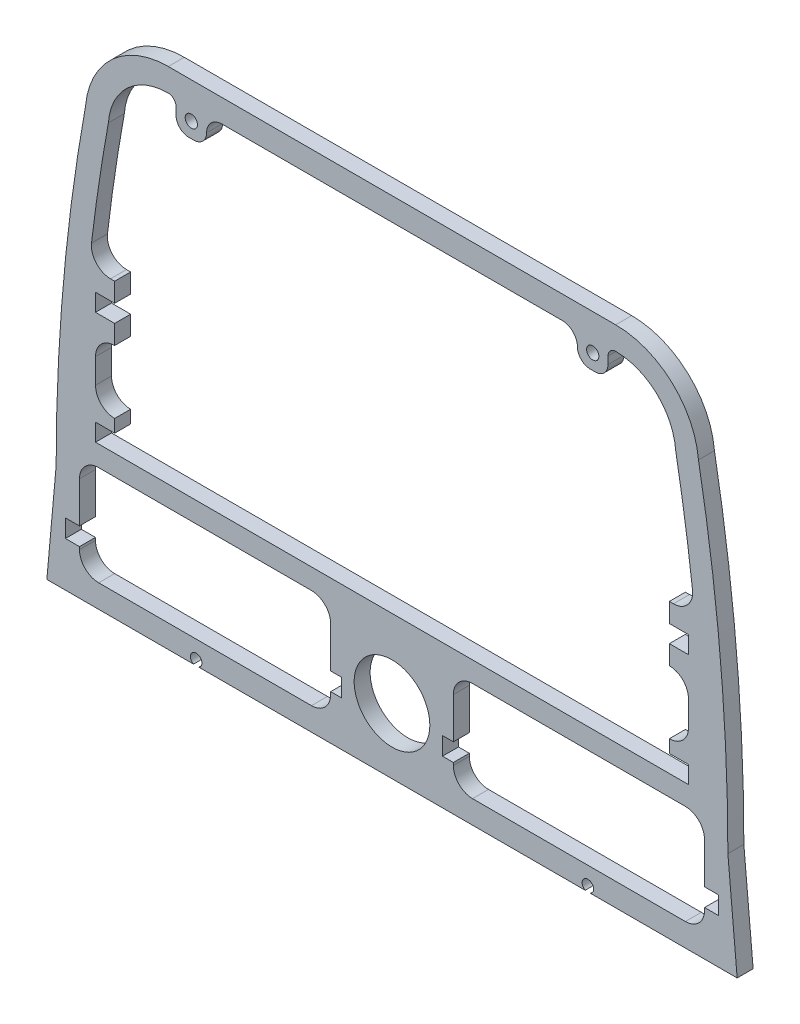
SolidWorks part; units mm, degrees
material "Delrin 2700 NC010, Low Viscosity Acetal Copolymer (SS)"
ref_plane "Front Plane" through (0, 0, 0) normal (0, 0, 1) x (1, 0, 0)
ref_plane "Top Plane" through (0, 0, 0) normal (0, 1, 0) x (1, 0, 0)
ref_plane "Right Plane" through (0, 0, 0) normal (1, 0, 0) x (0, 0, -1)
sketch "Sketch1" plane through (0, 0, 0) normal (0, 0, 1) x (1, 0, 0)
  line L0 (33.3676, -11.9888) -> (34.29, -22.225)
  line L1 (22.225, 27.94) -> (-22.225, 27.94)
  line L2 (-34.29, -22.225) -> (-30.4467, 20.4259) construction
  line L3 (-33.3676, -11.9888) -> (-33.3676, 14.6458) construction
  line L4 (-33.3676, -11.9888) -> (-34.29, -22.225)
  line L5 (16.9079, 25.654) -> (-16.9079, 25.654)
  line L6 (6.096, -17.78) -> (6.096, -19.939)
  line L7 (-31.0499, -19.939) -> (-6.096, -19.939)
  line L8 (-34.29, -22.225) -> (34.29, -22.225)
  line L9 (-31.0499, -10.033) -> (-31.0499, -16.002)
  line L10 (18.4213, 24.1407) -> (18.4213, 24.1363)
  line L11 (19.6913, 22.8663) -> (20.1867, 22.8663)
  line L12 (21.4567, 24.1363) -> (21.4567, 24.8713)
  line L13 (-21.4567, 24.1363) -> (-21.4567, 24.8713)
  line L14 (-19.6913, 22.8663) -> (-20.1867, 22.8663)
  line L15 (-18.4213, 24.1407) -> (-18.4213, 24.1363)
  line L16 (29.4572, -8.001) -> (-29.4572, -8.001)
  line L17 (31.0499, -10.033) -> (6.096, -10.033)
  line L18 (0, 18.415) -> (0, -18.415) construction
  line L19 (-1007.9925, 0) -> (48992.0075, 0) construction
  line L20 (-6.096, -10.033) -> (-31.0499, -10.033)
  line L21 (19.939, 24.384) -> (21.4567, 24.384) construction
  line L22 (6.096, -19.939) -> (31.0499, -19.939)
  line L23 (-6.096, -10.033) -> (-6.096, -16.002)
  line L24 (5.9491, -2.2098) -> (59.5431, -2.2098) construction
  line L25 (5.9491, -2.2098) -> (5.9491, -11.9888) construction
  line L26 (3.4091, -11.9888) -> (-3.4091, -11.9888) construction
  line L27 (59.5431, -2.2098) -> (59.5431, -11.9888) construction
  line L28 (-31.7887, -19.939) -> (31.7887, -19.939) construction
  line L29 (22.225, 25.654) -> (-22.225, 25.654) construction
  line L30 (-6.096, -19.939) -> (-6.1666, -19.9899)
  line L31 (29.4572, -6.2738) -> (27.5522, -6.2738)
  line L32 (27.5522, -6.2738) -> (27.5522, -5.0038)
  line L33 (-31.0499, -16.002) -> (-32.4469, -16.002)
  line L34 (27.5522, -5.0038) -> (29.4572, -5.0038)
  line L35 (29.4572, 1.27) -> (27.5522, 1.27)
  line L36 (27.5522, 1.27) -> (27.5522, 3.175)
  line L37 (27.5522, 3.175) -> (29.4572, 3.175)
  line L38 (29.4572, 4.9022) -> (27.5522, 4.9022)
  line L39 (19.939, 24.384) -> (18.4213, 24.384) construction
  line L40 (27.5522, 4.9022) -> (27.5522, 6.8072)
  line L41 (27.5522, 6.8072) -> (30.0922, 6.8072)
  line L42 (19.939, 24.384) -> (19.939, 22.8663) construction
  line L43 (6.096, -10.033) -> (6.096, -16.002)
  line L44 (-29.4572, -6.2738) -> (-29.4572, -8.001)
  line L45 (-29.4572, -6.2738) -> (-27.5522, -6.2738)
  line L46 (-27.5522, -6.2738) -> (-27.5522, -5.0038)
  line L47 (-27.5522, -5.0038) -> (-29.4572, -5.0038)
  line L48 (-29.4572, 1.27) -> (-29.4572, -5.0038)
  line L49 (-29.4572, 1.27) -> (-27.5522, 1.27)
  line L50 (-27.5522, 1.27) -> (-27.5522, 3.175)
  line L51 (-27.5522, 3.175) -> (-29.4572, 3.175)
  line L52 (-29.4572, 4.9022) -> (-29.4572, 3.175)
  line L53 (-32.4469, -16.002) -> (-32.4469, -17.78)
  line L54 (-32.4469, -17.78) -> (-31.0499, -17.78)
  line L55 (-6.096, -16.002) -> (-5.0149, -16.002)
  line L56 (-5.0149, -16.002) -> (-5.0149, -17.78)
  line L57 (-5.0149, -17.78) -> (-6.096, -17.78)
  line L58 (-31.0499, -10.033) -> (-31.0499, -19.939) construction
  line L59 (-31.0499, -14.986) -> (-34.8219, -14.986) construction
  line L60 (-31.0499, -14.986) -> (-1.8794, -14.986) construction
  line L61 (-6.096, -17.78) -> (-6.096, -19.939)
  line L62 (-31.0499, -19.939) -> (-31.0499, -17.78)
  line L63 (31.0499, -19.939) -> (31.0499, -17.78)
  line L64 (-31.0816, -12.0913) -> (-31.7887, -19.939) construction
  line L65 (31.0499, -10.033) -> (31.0499, -16.002)
  line L66 (32.4469, -17.78) -> (31.0499, -17.78)
  line L67 (32.4469, -16.002) -> (32.4469, -17.78)
  line L68 (31.0499, -16.002) -> (32.4469, -16.002)
  line L69 (6.096, -16.002) -> (5.0149, -16.002)
  line L70 (5.0149, -16.002) -> (5.0149, -17.78)
  line L71 (5.0149, -17.78) -> (6.096, -17.78)
  line L72 (29.4572, 4.9022) -> (29.4572, 3.175)
  line L73 (31.0816, -12.0913) -> (31.7887, -19.939) construction
  line L74 (29.4572, 1.27) -> (29.4572, -5.0038)
  line L75 (29.4572, -6.2738) -> (29.4572, -8.001)
  line L76 (-29.4572, 4.9022) -> (-27.5522, 4.9022)
  line L77 (-27.5522, 4.9022) -> (-27.5522, 6.8072)
  line L78 (-27.5522, 6.8072) -> (-30.0922, 6.8072)
  arc A0 (22.225, 27.94) -> (30.4467, 20.4259) centre (22.225, 19.685) cw
  arc A1 (-22.225, 27.94) -> (-30.4467, 20.4259) centre (-22.225, 19.685) ccw
  arc A2 (33.3676, -11.9888) -> (30.4467, 20.4259) centre (-147.9525, -11.9888) ccw
  circle A3 centre (0, -15.748) radius 3.7592
  circle A4 centre (19.4575, -21.717) radius 0.5715
  arc A5 (-33.3676, -11.9888) -> (-30.4467, 20.4259) centre (147.9525, -11.9888) cw
  arc A8 (20.1867, 22.8663) -> (21.4567, 24.1363) centre (20.1867, 24.1363) ccw
  circle A9 centre (-19.939, 24.384) radius 0.6096
  circle A10 centre (19.939, 24.384) radius 0.6096
  arc A11 (18.4213, 24.1363) -> (19.6913, 22.8663) centre (19.6913, 24.1363) ccw
  circle A12 centre (-19.4575, -21.717) radius 0.5715
  arc A13 (18.4213, 24.1407) -> (16.9079, 25.654) centre (16.9079, 24.1407) ccw
  arc A14 (22.2416, 25.654) -> (21.4567, 24.8713) centre (22.2394, 24.8713) ccw
  arc A15 (-22.2416, 25.654) -> (-21.4567, 24.8713) centre (-22.2394, 24.8713) cw
  arc A16 (-20.1867, 22.8663) -> (-21.4567, 24.1363) centre (-20.1867, 24.1363) cw
  arc A17 (-18.4213, 24.1363) -> (-19.6913, 22.8663) centre (-19.6913, 24.1363) cw
  arc A18 (-22.2416, 25.654) -> (-28.1777, 20.1262) centre (-22.225, 19.685) ccw
  arc A19 (-18.4213, 24.1407) -> (-16.9079, 25.654) centre (-16.9079, 24.1407) cw
  arc A20 (31.0816, -12.0913) -> (31.0816, -11.9888) centre (-147.9525, -11.9888) ccw
  arc A23 (22.2416, 25.654) -> (28.1777, 20.1262) centre (22.225, 19.685) cw
  arc A25 (-22.225, 25.654) -> (-28.1777, 20.1262) centre (-22.225, 19.685) ccw construction
  arc A26 (22.225, 25.654) -> (28.1777, 20.1262) centre (22.225, 19.685) cw construction
  arc A28 (-31.0816, -12.0913) -> (-28.1777, 20.1262) centre (147.9525, -11.9888) cw construction
  arc A30 (31.0816, -12.0913) -> (28.1777, 20.1262) centre (-147.9525, -11.9888) ccw construction
  arc A31 (30.0922, 6.8072) -> (28.1777, 20.1262) centre (-147.9525, -11.9888) ccw
  arc A33 (-30.0922, 6.8072) -> (-28.1777, 20.1262) centre (147.9525, -11.9888) cw
  point P0 (0, 0)
  point P1 (0, 27.94)
  point P26 (0, -22.225)
  point P31 (0, -11.9888)
  point P121 (-32.2988, -14.986)
  dimension "D4" = 2.286
  dimension "D6" = 8.255
  dimension "D7" = 19.4575
  dimension "D8" = 50.165
  dimension "D9" = 15.748
  dimension "D5" = 1.2192
  dimension "D17" = 1.143
  dimension "D3" = 7.5184
  dimension "D18" = 1.27
  dimension "D19" = 1.27
  dimension "D26" = 11.176
  dimension "D28" = 0.7827
  dimension "D29" = 1.5133
  dimension "D32" = 1.397
  dimension "D2" = 44.45
  dimension "D10" = 0.508
  dimension "D11" = 1.27
  dimension "D12" = 68.58
  dimension "D13" = 19.939
  dimension "D14" = 22.225
  dimension "D15" = 53.594
  dimension "D16" = 9.779
  dimension "D20" = 6.096
  dimension "D21" = 11.938
  dimension "D22" = 2.032
  dimension "D23" = 1.7272
  dimension "D24" = 1.27
  dimension "D25" = 1.905
  dimension "D27" = 0.4954
  dimension "D30" = 1.905
  dimension "D31" = 1.7272
  dimension "D33" = 1.778
  dimension "D34" = 2.159
  dimension "D35" = 24.9539
  dimension "D36" = 27.432
  dimension "D37" = 1.905
  dimension "D38" = 2.54
extrude "Boss-Extrude1" add sketch "Sketch1" along normal blind 1.5875 contours L8 A12 A4 L0 A2 A0 L1 A1 A5 L4 L74 L16 A18 A15 L13 A16 L14 A17 L15 A19 L5 A13 L10 A11 L11 A8 L12 A14 A23 A20 L22 L43 L17 A10 A9 A3 L20 region at (32.9825, -17.1832, 0)
ref_axis "Axis1" through (0, -15.748, 0) along (0, 0, 1)
fillet "Fillet1" radius 1.905 8 edges at (-6.096, -10.033, 0.7937) (6.096, -10.033, 0.7937) (-6.096, -19.939, 0.7937) (-31.0499, -19.939, 0.7937) (-31.0499, -10.033, 0.7937) (6.096, -19.939, 0.7937) (31.0499, -19.939, 0.7937) (31.0499, -10.033, 0.7937)
fillet "Fillet2" radius 1.905 6 edges at (-29.4572, 1.27, 0.7937) (-29.4572, -5.0038, 0.7937) (-30.0922, 6.8072, 0.7937) (29.4572, -5.0038, 0.7937) (29.4572, 1.27, 0.7937) (30.0922, 6.8072, 0.7937)
